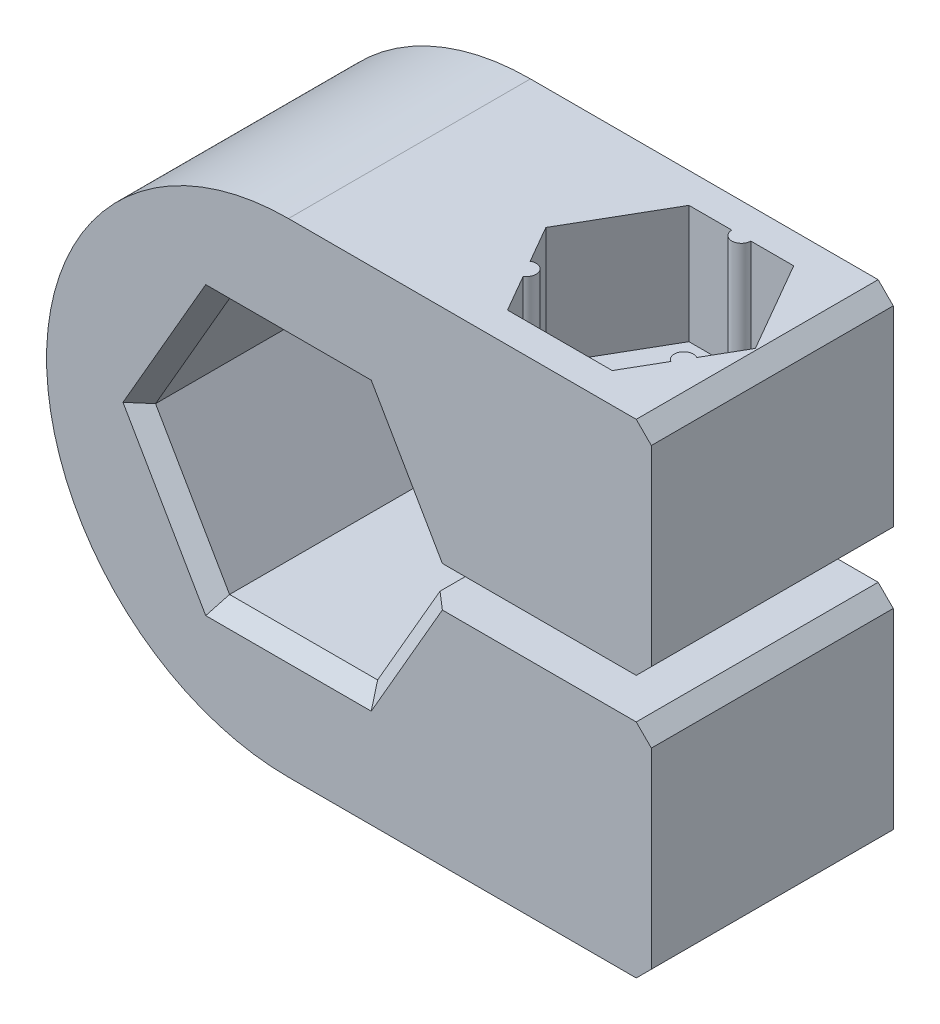
SolidWorks part; units mm, degrees
material "PET"
ref_plane "Front Plane" through (0, 0, 0) normal (0, 0, 1) x (1, 0, 0)
ref_plane "Top Plane" through (0, 0, 0) normal (0, 1, 0) x (1, 0, 0)
ref_plane "Right Plane" through (0, 0, 0) normal (1, 0, 0) x (0, 0, -1)
sketch "Sketch2" plane through (0, 0, 0) normal (0, 0, 1) x (1, 0, 0)
  line L0 (9.525, -12.7) -> (9.525, -1.0583) construction
  line L1 (3.8861, 6.731) -> (-3.8861, 6.731) construction
  line L2 (-3.8861, 6.731) -> (-7.7723, 0) construction
  line L3 (-7.7723, 0) -> (-3.8861, -6.731) construction
  line L4 (-3.8861, -6.731) -> (3.8861, -6.731) construction
  line L5 (3.8861, -6.731) -> (7.7723, 0) construction
  line L6 (7.7723, 0) -> (3.8861, 6.731) construction
  line L8 (3.8861, -6.731) -> (7.1613, -1.0583)
  line L9 (-3.8861, -6.731) -> (3.8861, -6.731)
  line L10 (-7.7723, 0) -> (-3.8861, -6.731)
  line L11 (-3.8861, 6.731) -> (-7.7723, 0)
  line L12 (3.8861, 6.731) -> (-3.8861, 6.731)
  line L13 (7.1613, 1.0583) -> (3.8861, 6.731)
  line L14 (9.525, 1.0583) -> (7.1613, 1.0583)
  line L15 (7.1613, -1.0583) -> (9.525, -1.0583)
  line L32 (9.525, 1.0583) -> (19.05, 1.0583)
  line L34 (19.05, 1.0583) -> (19.05, 12.7)
  line L36 (19.05, 12.7) -> (0, 12.7)
  line L37 (0, -12.7) -> (19.05, -12.7)
  line L39 (19.05, -12.7) -> (19.05, -1.0583)
  line L41 (19.05, -1.0583) -> (9.525, -1.0583)
  line L48 (15.875, 1.0583) -> (8.9943, 1.0583) construction
  line L49 (0, 12.7) -> (15.875, 12.7) construction
  circle A0 centre (0, 0) radius 6.731 construction
  arc A2 (0, 12.7) -> (0, -12.7) centre (0, 0) ccw
  point P46 (-12.7, 0)
  dimension "D2" = 31.75
  dimension "D1" = 13.462
extrude "Boss-Extrude1" add sketch "Sketch2" along normal blind 12.7
chamfer "Chamfer1" distance 0.7937 angle 45 16 edges at (5.5237, -3.8947, 0) (0, -6.731, 0) (-5.8292, -3.3655, 0) (-5.8292, 3.3655, 0) (0, 6.731, 0) (5.5237, 3.8947, 0) (5.5237, 3.8947, 12.7) (0, 6.731, 12.7) (-5.8292, 3.3655, 12.7) (-5.8292, -3.3655, 12.7) (0, -6.731, 12.7) (5.5237, -3.8947, 12.7) (19.05, -12.7, 6.35) (19.05, 12.7, 6.35) (19.05, 1.0583, 6.35) (19.05, -1.0583, 6.35)
sketch "Sketch3" plane through (0, 12.7, 0) normal (0, 1, 0) x (1, 0, 0)
  line L0 (7.1613, -11.9062) -> (7.1613, -0.7938) construction
  line L1 (15.4102, -11.1125) -> (18.1598, -6.35)
  line L2 (19.05, -12.7) -> (19.05, 0) construction
  line L5 (18.1598, -6.35) -> (15.4102, -1.5875)
  line L6 (15.4102, -1.5875) -> (9.9109, -1.5875)
  line L7 (9.9109, -1.5875) -> (7.1613, -6.35)
  line L8 (7.1613, -6.35) -> (9.9109, -11.1125)
  line L9 (9.9109, -11.1125) -> (15.4102, -11.1125)
  circle A0 centre (12.6605, -6.35) radius 2.4892
  circle A1 centre (12.6605, -6.35) radius 4.7625 construction
  point P2 (16.5957, -11.1125)
  point P7 (19.05, -6.35)
  point P13 (7.434, -6.35)
  dimension "D1" = 4.9784
  dimension "D2" = 9.525
extrude "Cut-Extrude1" cut sketch "Sketch3" against normal through all contours A0 region at (12.6605, 12.7, 6.35)
sketch "Sketch4" plane through (0, 12.7, 0) normal (0, 1, 0) x (1, 0, 0)
  line L1 (9.9109, -11.1125) -> (15.4102, -11.1125)
  line L2 (15.4102, -11.1125) -> (18.1598, -6.35)
  line L3 (18.1598, -6.35) -> (15.4102, -1.5875)
  line L4 (15.4102, -1.5875) -> (9.9109, -1.5875)
  line L5 (9.9109, -1.5875) -> (7.1613, -6.35)
  line L6 (7.1613, -6.35) -> (9.9109, -11.1125)
  circle A0 centre (12.6605, -6.35) radius 4.7625 construction
  dimension "D1" = 9.525
extrude "Cut-Extrude2" cut sketch "Sketch4" against normal blind 6.2
sketch "Sketch5" plane through (0, -12.7, 0) normal (0, -1, 0) x (1, 0, 0)
  circle A0 centre (12.6605, 6.35) radius 4.064
  dimension "D1" = 8.128
extrude "Cut-Extrude3" cut sketch "Sketch5" against normal blind 6.35
chamfer "Chaflán1" distance 0.7937 angle 45 3 edges at (16.7245, -12.7, 6.35) (15.1497, -1.0583, 6.35) (12.6605, 1.0583, 8.8392)
sketch "Croquis3" plane through (0, 12.7, 0) normal (0, 1, 0) x (1, 0, 0)
  line L0 (15.4102, -1.5875) -> (9.9109, -1.5875) construction
  line L1 (7.1613, -6.35) -> (9.9109, -11.1125) construction
  line L2 (15.4102, -11.1125) -> (18.1598, -6.35) construction
  circle A0 centre (12.6605, -1.5875) radius 0.4978
  circle A1 centre (8.5361, -8.7312) radius 0.4978
  circle A2 centre (16.785, -8.7312) radius 0.4978
  dimension "D1" = 0.9957
extrude "Saliente-Extruir1" add sketch "Croquis3" against normal up to surface (6.2 mm away) up to face at (12.6605, 6.5, 6.35)
